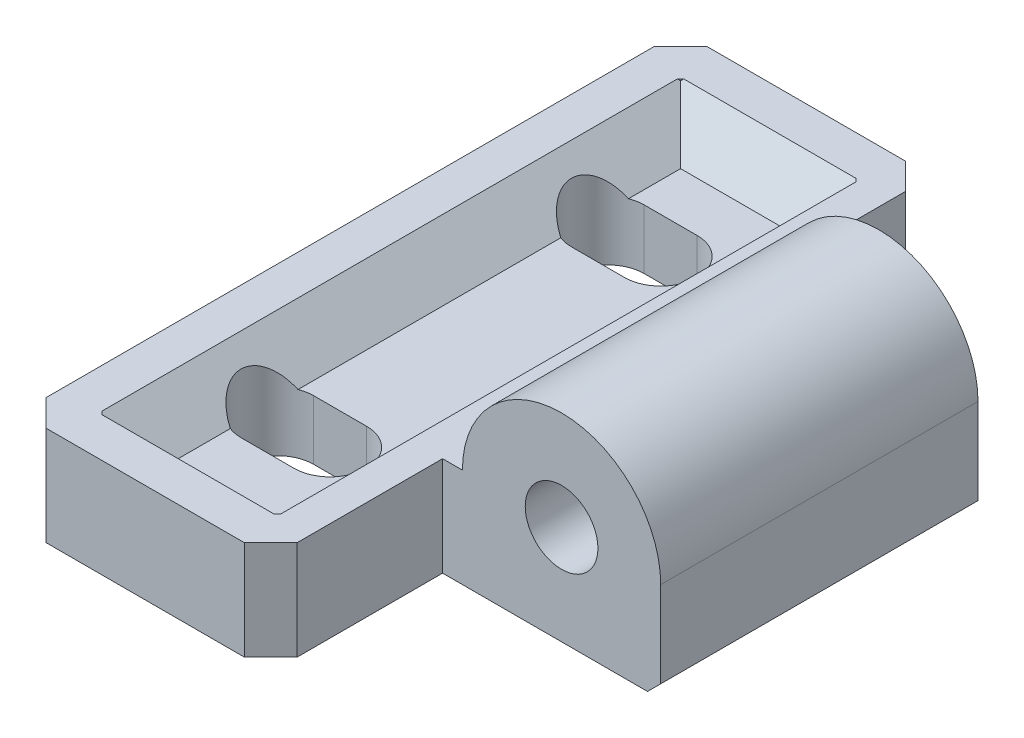
SolidWorks part; units mm, degrees
ref_plane "Front Plane" through (0, 0, 0) normal (0, 0, 1) x (1, 0, 0)
ref_plane "Top Plane" through (0, 0, 0) normal (0, 1, 0) x (1, 0, 0)
ref_plane "Right Plane" through (0, 0, 0) normal (1, 0, 0) x (0, 0, -1)
sketch "contour" plane through (0, 0, 0) normal (0, 0, 1) x (1, 0, 0)
  line L0 (0, -7.5) -> (6.5, -7.5)
  line L1 (-7.5, -0.0001) -> (-28, -0.0001)
  line L2 (7.5, -6.5) -> (7.5, 0)
  line L3 (0, -7.5) -> (-28, -7.5)
  line L4 (-28, -0.0001) -> (-28, -7.5)
  line L5 (6.5, -7.5) -> (7.5, -6.5)
  arc A0 (7.5, 0) -> (-7.5, -0.0001) centre (0, 0) ccw
  point P6 (7.5, -7.5)
  dimension "D2" = 15
  dimension "D1" = 7.4999
  dimension "D3" = 28
extrude "Boss-Extrude1" add sketch "contour" along normal mid plane 50
sketch "Sketch6" plane through (0, -7.5, 0) normal (0, -1, 0) x (1, 0, 0)
  line L0 (-28, 25) -> (-28, -25) construction
  line L1 (-28, 25) -> (6.5, 25) construction
  line L2 (-21, 12.5) -> (-17, 12.5) construction
  line L3 (-21, 15.25) -> (-17, 15.25)
  line L4 (-21, 9.75) -> (-17, 9.75)
  line L5 (-21, -12.5) -> (-17, -12.5) construction
  line L6 (-21, -9.75) -> (-17, -9.75)
  line L7 (-21, -15.25) -> (-17, -15.25)
  circle A0 centre (-19, 12.5) radius 2.75 construction
  circle A1 centre (-19, -12.5) radius 2.75 construction
  arc A2 (-21, 15.25) -> (-21, 9.75) centre (-21, 12.5) ccw
  arc A3 (-17, 9.75) -> (-17, 15.25) centre (-17, 12.5) ccw
  arc A4 (-21, -9.75) -> (-21, -15.25) centre (-21, -12.5) ccw
  arc A5 (-17, -15.25) -> (-17, -9.75) centre (-17, -12.5) ccw
  point P10 (-19, 12.5)
  point P17 (-19, -12.5)
  dimension "D1" = 5.5
  dimension "D2" = 9
  dimension "D5" = 4
  dimension "D3" = 12.5
  dimension "D4" = 25
extrude "mount-holes" cut sketch "Sketch6" against normal through all
sketch "Sketch7" plane through (0, -7.5, 0) normal (0, -1, 0) x (1, 0, 0)
  line L1 (-9, 12) -> (7.5, 12)
  line L2 (-9, 12) -> (-9, 25)
  line L3 (-9, 25) -> (7.5, 25)
  line L4 (7.5, 12) -> (7.5, 25)
  line L7 (-9, -12) -> (7.5, -12)
  line L8 (-9, -12) -> (-9, -25)
  line L9 (-9, -25) -> (7.5, -25)
  line L10 (7.5, -12) -> (7.5, -25)
  line L11 (7.5, 25) -> (7.5, -25) construction
  line L12 (-28, -25) -> (6.5, -25) construction
  line L13 (-28, 25) -> (6.5, 25) construction
  dimension "D3" = 16.5
extrude "cut-part" cut sketch "Sketch7" against normal blind 20
sketch "Sketch10" plane through (0, 0, 0) normal (0, 0, 1) x (1, 0, 0)
  circle A0 centre (0, 0) radius 2.75
  dimension "D1" = 5.5
extrude "Cut-Extrude3" cut sketch "Sketch10" against normal mid plane 50
chamfer "Chamfer1" distance 2 angle 45 4 edges at (-9, -3.75, -25) (-28, -3.75, -25) (-28, -3.75, 25) (-9, -3.75, 25)
sketch "Sketch11" plane through (0, -0.0001, 0) normal (0, 1, 0) x (1, 0, 0)
  line L36 (-11.5, -21.7574) -> (-11.5, 21.7574)
  line L37 (-11.5, 21.7574) -> (-11.7426, 22)
  line L38 (-11.7426, 22) -> (-24.7574, 22)
  line L39 (-24.7574, 22) -> (-25, 21.7574)
  line L40 (-25, 21.7574) -> (-25, -21.7574)
  line L41 (-25, -21.7574) -> (-24.7574, -22)
  line L42 (-24.7574, -22) -> (-11.7426, -22)
  line L43 (-11.7426, -22) -> (-11.5, -21.7574)
extrude "Cut-Extrude4" cut sketch "Sketch11" against normal blind 3
chamfer "Chamfer2" distance 3 angle 45 4 edges at (-11.5, -3.0001, 0) (-18.25, -3.0001, 22) (-25, -3.0001, 0) (-18.25, -3.0001, -22)
